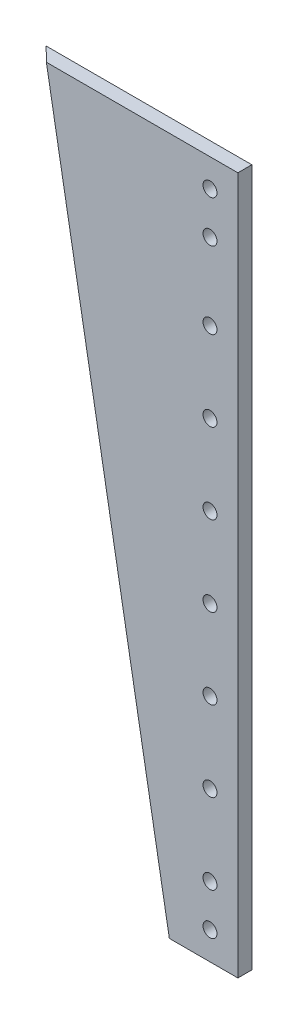
SolidWorks part; units mm, degrees
ref_plane "Front Plane" through (0, 0, 0) normal (0, 0, 1) x (1, 0, 0)
ref_plane "Top Plane" through (0, 0, 0) normal (0, 1, 0) x (1, 0, 0)
ref_plane "Right Plane" through (0, 0, 0) normal (1, 0, 0) x (0, 0, -1)
sketch "Sketch1" plane through (0, 0, 0) normal (0, 0, 1) x (1, 0, 0)
  line L1 (-60, 200) -> (0, 200)
  line L2 (-60, 200) -> (-60, 0)
  line L3 (-60, 0) -> (0, 0)
  line L4 (0, 200) -> (0, 0)
  dimension "D1" = 60
  dimension "D2" = 200
extrude "Boss-Extrude1" add sketch "Sketch1" along normal blind 4
sketch "Sketch6" plane through (0, 0, 0) normal (0, 0, 1) x (1, 0, 0)
  line L0 (-60, 0) -> (0, 0) construction
  line L1 (0, 0) -> (0, 200) construction
  circle A0 centre (-8, 8) radius 2
  circle A1 centre (-8, 20) radius 2
  dimension "D1" = 4
  dimension "D2" = 8
  dimension "D3" = 12
  dimension "D4" = 8
extrude "Cut-Extrude3" cut sketch "Sketch6" along normal up to surface (4 mm away) up to face at (-30, 100, 4)
ref_plane "Plane1" through (0, 100, 0) normal (0, 1, 0) x (1, 0, 0)
mirror "Mirror1" about plane through (0, 100, 0) normal (0, 1, 0) of "Cut-Extrude3"
sketch "Sketch7" plane through (0, 0, 0) normal (0, 0, 1) x (1, 0, 0)
  line L0 (-8, 43) -> (-8, 20) construction
  circle A0 centre (-8, 43) radius 2
  dimension "D2" = 4
  dimension "D1" = 23
extrude "Cut-Extrude4" cut sketch "Sketch7" along normal up to surface (4 mm away) up to face at (-6, 192, 4)
pattern_linear "LPattern1" count 6 spacing 23 along (0, 1, 0) of "Cut-Extrude4"
sketch "Sketch3" plane through (-200, 0, 0) normal (0, 0, -1) x (-1, 0, 0)
  line L8 (-140, 0) -> (-175.2654, 0)
  line L9 (-140, 0) -> (-200, 0) construction
  line L10 (-140, 200) -> (-140, 0) construction
  line L11 (-175.2654, 0) -> (-140, 200)
  line L12 (-140, 200) -> (-140, 0)
  line L13 (-154.1062, 0) -> (-154.1062, 120) construction
  dimension "D1" = 10
  dimension "D2" = 120
  dimension "D3" = 21.1592
extrude "傾斜刀" cut sketch "Sketch3" against normal up to surface (4 mm away) up to face at (-6, 66, 4)
chamfer "傾斜刀倒角" distance 5 angle 45 1 edges at (-42.3673, 100, 4)
chamfer "垂直刀倒角" [suppressed] distance 5 angle 45
